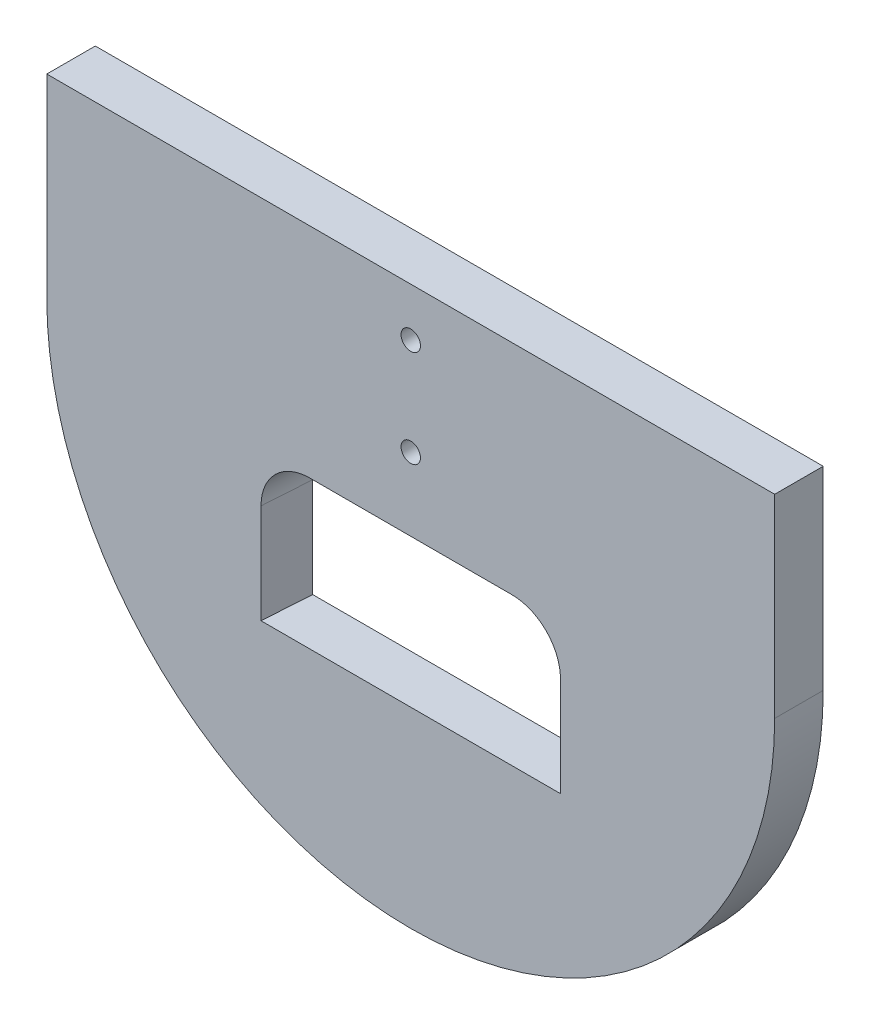
SolidWorks part; units mm, degrees
ref_plane "Front Plane" through (0, 0, 0) normal (0, 0, 1) x (1, 0, 0)
ref_plane "Top Plane" through (0, 0, 0) normal (0, 1, 0) x (1, 0, 0)
ref_plane "Right Plane" through (0, 0, 0) normal (1, 0, 0) x (0, 0, -1)
sketch "Sketch1" plane through (0, 0, 0) normal (0, 0, 1) x (1, 0, 0)
  line L0 (0, -40) -> (0, 0)
  line L1 (0, 0) -> (-150, 0)
  line L2 (-150, 0) -> (-150, -40)
  line L4 (-105.205, -45) -> (-44.795, -45)
  line L5 (-105.205, -45) -> (-105.205, -75.5)
  line L6 (-105.205, -75.5) -> (-44.795, -75.5)
  line L7 (-44.795, -45) -> (-44.795, -75.5)
  arc A0 (0, -40) -> (-150, -40) centre (-75, -40) cw
  circle A1 centre (-75, -30) radius 2
  circle A2 centre (-75, -10) radius 2
  point P6 (-75, -45)
  point P11 (-75, 0)
  point P16 (0, 0)
  dimension "D1" = 75
  dimension "D6" = 4
  dimension "D7" = 20
  dimension "D8" = 15
  dimension "D2" = 40
  dimension "D3" = 60.41
  dimension "D4" = 30.5
  dimension "D5" = 45
  dimension "D10" = 44.795
extrude "Boss-Extrude1" add sketch "Sketch1" along normal blind 10
chamfer "Chamfer1" distance 10 angle 3.71 2 edges at (-44.795, -60.25, 10) (-105.205, -60.25, 10) first distance on face at (-44.795, -60.25, 5) first distance on face at (-105.205, -60.25, 5)
fillet "Fillet1" radius 10 2 edges at (-105.5292, -45, 5) (-44.4708, -45, 5)
